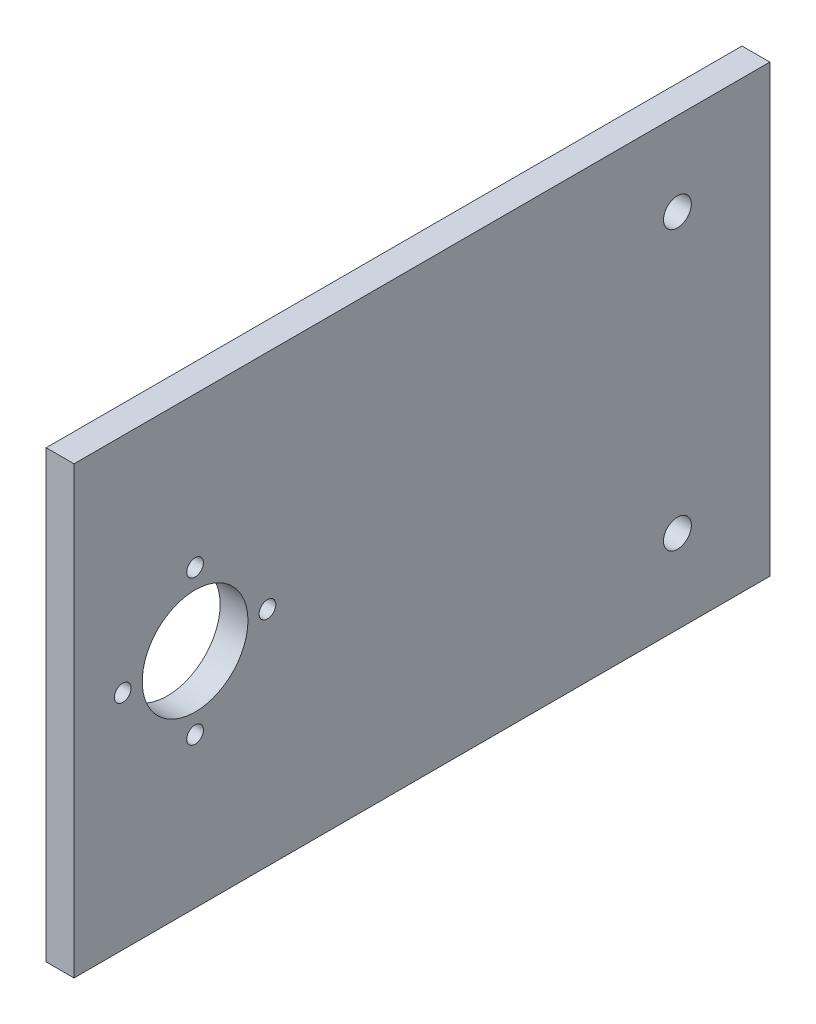
SolidWorks part; units mm, degrees
ref_plane "Front Plane" through (0, 0, 0) normal (1, 0, 0) x (0, 1, 0)
ref_plane "Top Plane" through (0, 0, 0) normal (0, 0, 1) x (0, 1, 0)
ref_plane "Right Plane" through (0, 0, 0) normal (0, 1, 0) x (-1, 0, 0)
sketch "Sketch1" plane through (0, 0, 0) normal (1, 0, 0) x (0, 1, 0)
  line L0 (-40, 40.75) -> (40, 40.75) construction
  line L1 (-40, -62.5) -> (40, -62.5)
  line L2 (-40, -62.5) -> (-40, 62.5)
  line L3 (-40, 62.5) -> (40, 62.5)
  line L4 (40, -62.5) -> (40, 62.5)
  line L5 (-40, -62.5) -> (40, 62.5) construction
  line L6 (-40, 62.5) -> (40, -62.5) construction
  line L7 (0, 62.5) -> (0, -62.5) construction
  line L8 (-40, -45.9) -> (40, -45.9) construction
  circle A1 centre (0, 53.75) radius 1.5
  circle A2 centre (0, 27.75) radius 1.5
  circle A3 centre (-13, 40.75) radius 1.5
  circle A4 centre (13, 40.75) radius 1.5
  circle A5 centre (0, 40.75) radius 9.5
  circle A6 centre (-25, -45.9) radius 2.5
  circle A7 centre (25, -45.9) radius 2.5
  point P0 (0, 0)
  dimension "D5" = 13
  dimension "D4" = 3
  dimension "D6" = 3
  dimension "D8" = 19
  dimension "D10" = 5
  dimension "D1" = 125
  dimension "D2" = 80
  dimension "D3" = 103.25
  dimension "D7" = 13
  dimension "D9" = 16.6
  dimension "D11" = 25
extrude "Boss-Extrude1" add sketch "Sketch1" along normal blind 5
